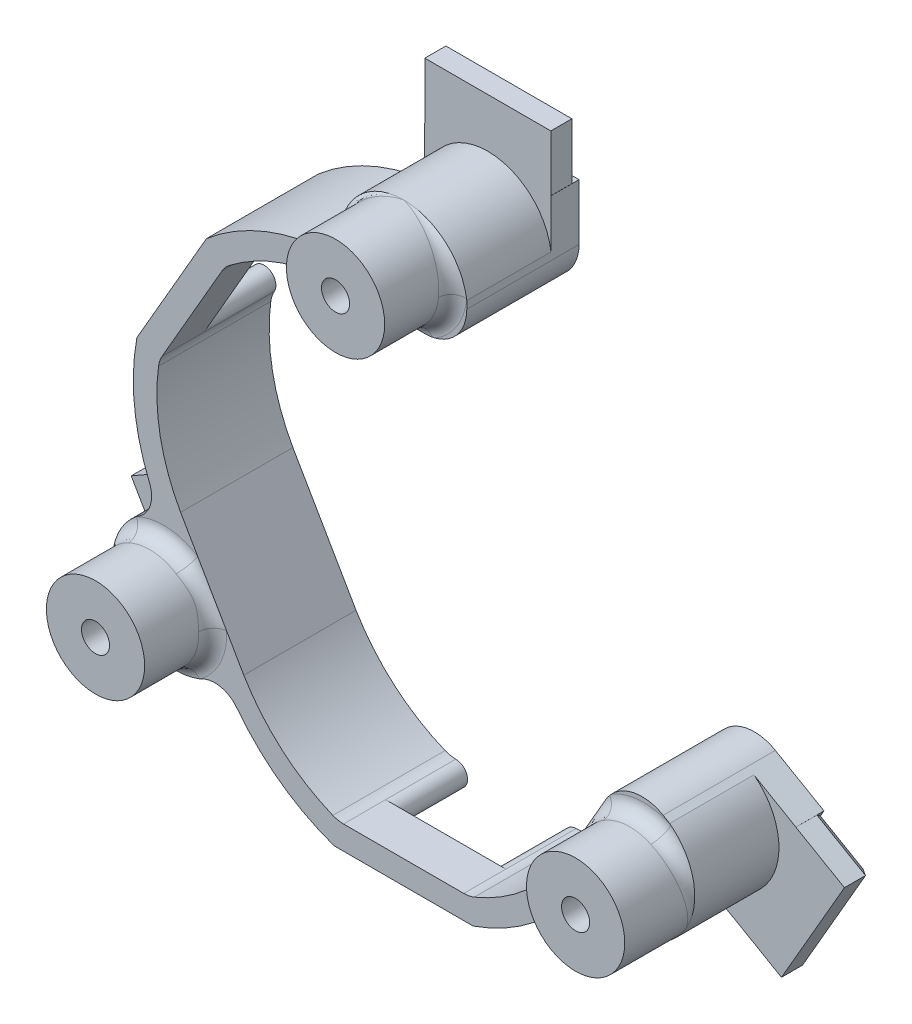
SolidWorks part; units mm, degrees
ref_plane "Front Plane" through (0, 0, 0) normal (0, 0, 1) x (1, 0, 0)
ref_plane "Top Plane" through (0, 0, 0) normal (0, 1, 0) x (1, 0, 0)
ref_plane "Right Plane" through (0, 0, 0) normal (1, 0, 0) x (0, 0, -1)
sketch "Sketch1" plane through (0, 0, 0) normal (0, 0, 1) x (1, 0, 0)
  line L0 (-4.5, 22.75) -> (4.5, 22.75) construction
  line L1 (-4.5, 22.75) -> (-4.5, 26.75)
  line L2 (-4.5, 26.75) -> (4.5, 26.75)
  line L3 (4.5, 26.75) -> (4.5, 22.75)
  line L4 (-4.5, 22.75) -> (-4.5, 15.75)
  line L5 (-4.5, 15.75) -> (4.5, 15.75)
  line L6 (4.5, 15.75) -> (4.5, 22.75)
  circle A0 centre (0, 0) radius 22.75 construction
  point P5 (0, 22.75)
  point P6 (0, 15.75)
  dimension "D1" = 45.5
  dimension "D2" = 9
  dimension "D3" = 4
  dimension "D4" = 7
extrude "Boss-Extrude1" add sketch "Sketch1" along normal blind 2
sketch "Sketch2" plane through (0, 0, 2) normal (0, 0, 1) x (1, 0, 0)
  line L0 (4.5, 15.75) -> (4.5, 26.75) construction
  line L1 (-4.5, 15.75) -> (4.5, 15.75)
  line L2 (-4.5, 15.75) -> (-4.5, 23.75)
  line L3 (-4.5, 23.75) -> (4.5, 23.75)
  line L4 (4.5, 15.75) -> (4.5, 23.75)
  line L5 (4.5, 26.75) -> (-4.5, 26.75) construction
  dimension "D1" = 3
extrude "Boss-Extrude2" add sketch "Sketch2" along normal blind 10.85
sketch "Sketch5" plane through (0, 0, 12.85) normal (0, 0, 1) x (1, 0, 0)
  line L0 (0, 15.75) -> (0, 23.75) construction
  line L1 (-4.5, 15.75) -> (4.5, 15.75) construction
  line L2 (4.5, 23.75) -> (-4.5, 23.75) construction
  circle A0 centre (0, 19.75) radius 1
  point P0 (0, 0)
  point P10 (0, 19.75)
  dimension "D2" = 2
  dimension "D1" = 19.75
extrude "Cut-Extrude1" cut sketch "Sketch5" against normal through all
sketch "Sketch17" plane through (0, 0, 0) normal (0, 0, -1) x (-1, 0, 0)
  line L0 (4.49, 26.75) -> (4.49, 22.75)
  line L1 (-4.5, 26.75) -> (4.5, 26.75) construction
  line L2 (4.49, 22.75) -> (-4.49, 22.75) construction
  line L3 (-4.49, 22.75) -> (-4.49, 26.75)
  line L4 (4.49, 22.75) -> (4.5, 22.75)
  line L5 (4.5, 26.75) -> (4.5, 15.75) construction
  line L6 (-4.5, 15.75) -> (-4.5, 26.75) construction
  line L7 (4.5, 23.75) -> (-4.5, 23.75) construction
  line L8 (4.5, 22.75) -> (4.5, 26.75)
  line L9 (4.5, 26.75) -> (4.49, 26.75)
  line L10 (-4.49, 22.75) -> (-4.5, 22.75)
  line L11 (-4.5, 22.75) -> (-4.5, 26.75)
  line L12 (-4.5, 26.75) -> (-4.49, 26.75)
  point P4 (4.5, 23.75)
  point P7 (-4.5, 23.75)
  dimension "D1" = 1
  dimension "D2" = 0.01
  dimension "D3" = 0.01
extrude "Cut-Extrude7" cut sketch "Sketch17" against normal up to surface (2 mm away) up to face at (1.125, 25.25, 2)
ref_axis "Axis1" through (0, 0, -0.6425) along (0, 0, 1)
pattern_circular "CirPattern1" count 3 over 360 about axis through (0, 0, -0.6425) along (0, 0, 1) of bodies 124 104
sketch "Sketch3" plane through (0, 0, 0) normal (0, 0, -1) x (-1, 0, 0)
  line L0 (-11.3899, -11.7721) -> (11.3899, -11.7721) construction
  line L2 (0, 0) -> (-13.6399, -7.875) construction
  line L3 (-15.8899, -3.9779) -> (-11.3899, -11.7721) construction
  line L4 (0, 0) -> (-4.0622, -15.1603) construction
  line L5 (-11.3899, -11.7721) -> (-17.4521, -15.2721) construction
  line L6 (-12.8449, -12.6122) -> (-11.3899, -11.7721)
  line L7 (12.8449, -12.6122) -> (11.3899, -11.7721)
  line L8 (0, 0) -> (13.6399, -7.875) construction
  line L9 (11.3899, -11.7721) -> (15.8899, -3.9779) construction
  line L10 (17.3449, -4.8179) -> (15.8899, -3.9779)
  line L11 (4.5, 17.4301) -> (4.5, 15.75)
  line L14 (4.9592, -19.0834) -> (-4.9592, -19.0834)
  line L15 (-4.6632, -17.4034) -> (4.6632, -17.4034)
  line L18 (17.4034, 4.6632) -> (12.7402, 12.7402)
  line L19 (14.0471, 13.8365) -> (19.0064, 5.2469)
  arc A0 (-11.3899, -11.7721) -> (-4.6632, -17.4034) centre (0, -5) ccw
  arc A1 (-12.8449, -12.6122) -> (-4.9592, -19.0834) centre (0, -5) ccw
  arc A4 (11.3899, -11.7721) -> (4.6632, -17.4034) centre (0, -5) cw
  arc A5 (12.8449, -12.6122) -> (4.9592, -19.0834) centre (0, -5) cw
  arc A6 (17.3449, -4.8179) -> (19.0064, 5.2469) centre (4.3301, 2.5) ccw
  arc A7 (15.8899, -3.9779) -> (17.4034, 4.6632) centre (4.3301, 2.5) ccw
  arc A10 (4.5, 17.4301) -> (14.0471, 13.8365) centre (4.3301, 2.5) cw
  arc A11 (4.5, 15.75) -> (12.7402, 12.7402) centre (4.3301, 2.5) cw
  point P7 (0, -5)
  point P11 (0, -19.5)
  point P22 (0, -11.7721)
  dimension "D4" = 1.68
  dimension "D5" = 1.68
  dimension "D1" = 5
  dimension "D2" = 19.5
  dimension "D3" = 45
extrude "Boss-Extrude3" add sketch "Sketch3" against normal blind 8
sketch "Sketch13" plane through (0, 0, 12.85) normal (0, 0, 1) x (1, 0, 0)
  circle A0 centre (-17.104, -9.875) radius 3.5
  circle A1 centre (-17.104, -9.875) radius 6.0208
  circle A2 centre (0, 19.75) radius 3.5
  circle A3 centre (0, 19.75) radius 6.0208
  circle A4 centre (17.104, -9.875) radius 3.5
  circle A5 centre (17.104, -9.875) radius 6.0208
extrude "Cut-Extrude4" cut sketch "Sketch13" against normal up to surface (4.85 mm away) up to face at (0, -15.5346, 8)
fillet "Fillet1" radius 2 4 edges at (12.8449, -12.6122, 4) (-12.8449, -12.6122, 4) (-17.3449, -4.8179, 4) (-4.5, 17.4301, 4)
sketch "Sketch16" plane through (0, 0, 8) normal (0, 0, 1) x (1, 0, 0)
  line L0 (4.5, 19.2915) -> (4.5, 24.6619)
  line L1 (-4.5, 19.2915) -> (-4.5, 24.6619)
  line L2 (-4.5, 24.6619) -> (4.5, 24.6619)
  line L3 (15.8899, -3.9779) -> (22.8181, -7.9779) construction
  line L4 (-17.104, -9.875) -> (-20.5681, -11.875) construction
  line L5 (-18.3181, -15.7721) -> (-22.8181, -7.9779) construction
  line L6 (17.104, -9.875) -> (20.5681, -11.875) construction
  line L7 (22.8181, -7.9779) -> (18.3181, -15.7721) construction
  line L8 (0, 19.75) -> (0, 23.75) construction
  line L9 (-4.5, 23.75) -> (4.5, 23.75) construction
  arc A0 (4.5, 19.2915) -> (-4.5, 19.2915) centre (0, 18.713) ccw
  arc A1 (-18.9569, -5.7486) -> (-14.4569, -13.5428) centre (-16.2059, -9.3565) ccw
  arc A2 (-14.4569, -13.5428) -> (-18.9569, -5.7486) centre (-19.7218, -11.3864) cw
  arc A3 (14.4569, -13.5428) -> (18.9569, -5.7486) centre (16.2059, -9.3565) ccw
  arc A4 (18.9569, -5.7486) -> (14.4569, -13.5428) centre (19.3047, -11.1456) cw
  circle A5 centre (-17.104, -9.875) radius 3.5 construction
  circle A6 centre (17.104, -9.875) radius 3.5 construction
  circle A7 centre (0, 19.75) radius 3.5 construction
  point P26 (-20.1351, -11.625)
  point P34 (20.1351, -11.625)
  point P42 (0, 23.25)
  line M31 (-4.5, 23.75) -> (-4.5, 19.2915)
  line M37 (-18.9569, -5.7486) -> (-22.8181, -7.9779)
  line M38 (-22.8181, -7.9779) -> (-18.3181, -15.7721)
  line M39 (-18.3181, -15.7721) -> (-14.4569, -13.5428)
  line M45 (14.4569, -13.5428) -> (18.3181, -15.7721)
extrude "Cut-Extrude5" cut sketch "Sketch16" against normal up to surface (6 mm away) contours A3 M45 | A0 L0 M31 | A1 M37 M38 M39 region at (0, 23.2809, 8) region at (-20.2481, -11.6903, 8) region at (20.9999, -12.1243, 8) up to face at (21.3059, -13.5971, 2)
fillet "Fillet3" radius 2 4 edges at (4.6632, -17.4034, 4) (-4.6632, -17.4034, 4) (-17.4034, 4.6632, 4) (-12.7402, 12.7402, 4)
fillet "Fillet8" radius 1 3 edges at (13.604, -9.875, 8) (-20.604, -9.875, 8) (-3.5, 19.75, 8)
chamfer "Chamfer1" distance 0.5 angle 45 9 edges at (23.1662, -13.375, 0) (0, 26.75, 0) (-23.1662, -13.375, 0) (-4.49, 24.75, 0) (4.49, 24.75, 0) (23.6791, -8.4865, 0) (19.1891, -16.2635, 0) (-19.1891, -16.2635, 0) (-23.6791, -8.4865, 0) tangent propagation no
chamfer "Chamfer2" [suppressed] distance 0.2 angle 45
sketch "Sketch19" plane through (0, 0, 0) normal (0, 0, -1) x (-1, 0, 0)
  line L0 (12.9297, 12.412) -> (14.3846, 13.252)
  line L1 (19.0064, 5.2469) -> (14.0471, 13.8365) construction
  line L2 (17.214, 4.9914) -> (18.6689, 5.8314)
  line L3 (18.6689, 5.8314) -> (14.3846, 13.252)
  line L4 (12.9297, 12.412) -> (17.214, 4.9914)
  line L10 (4.2843, -17.4034) -> (4.2843, -19.0834)
  line L11 (-4.9592, -19.0834) -> (4.9592, -19.0834) construction
  line L12 (-4.2843, -17.4034) -> (-4.2843, -19.0834)
  line L13 (-4.2843, -19.0834) -> (4.2843, -19.0834)
  line L14 (4.2843, -17.4034) -> (-4.2843, -17.4034)
extrude "Cut-Extrude8" cut sketch "Sketch19" against normal blind 5
sketch "Sketch20" plane through (0, 0, 0) normal (0, 0, -1) x (-1, 0, 0)
  line L0 (14.3846, 13.252) -> (12.9297, 12.412) construction
  line L1 (17.214, 4.9914) -> (18.6689, 5.8314) construction
  line L2 (4.2843, -19.0834) -> (4.2843, -17.4034) construction
  line L3 (-4.2843, -17.4034) -> (-4.2843, -19.0834) construction
  circle A0 centre (13.6571, 12.832) radius 0.84
  circle A1 centre (17.9414, 5.4114) radius 0.84
  circle A2 centre (4.2843, -18.2434) radius 0.84
  circle A3 centre (-4.2843, -18.2434) radius 0.84
extrude "Boss-Extrude8" add sketch "Sketch20" against normal up to surface (5 mm away) up to face at (0, -18.2434, 5)
fillet "Fillet12" radius 3 2 edges at (15.8899, -3.9779, 4) (4.5, 15.75, 4)
sketch "Sketch6" plane through (0, 0, 0) normal (0, 0, -1) x (-1, 0, 0)
  line L0 (7.1492, -21.7889) -> (2.9426, -12.7167)
  line L1 (2.9426, -12.7167) -> (-2.9668, -12.7167)
  line L2 (-2.9668, -12.7167) -> (-7.125, -21.7889)
  line L3 (-7.125, -21.7889) -> (7.1492, -21.7889)
  line L4 (-15.3072, 17.0648) -> (-22.4443, 4.703)
  line L5 (-9.5296, 8.9277) -> (-15.3072, 17.0648)
  line L6 (-22.4443, 4.703) -> (-12.4843, 3.81)
  line L7 (-12.4843, 3.81) -> (-9.5296, 8.9277)
  line L8 (22.4322, 4.724) -> (15.2951, 17.0858)
  line L9 (12.4964, 3.789) -> (22.4322, 4.724)
  line L10 (15.2951, 17.0858) -> (9.5417, 8.9067)
  line L11 (9.5417, 8.9067) -> (12.4964, 3.789)
  line L12 (0, 0) -> (2.9426, -12.7167) construction
  line L13 (4.2843, -17.4034) -> (-4.2843, -17.4034) construction
  dimension "D1" = 10
  dimension "D2" = 13.0527
extrude "Cut-Extrude2" [suppressed] cut sketch "Sketch6" against normal blind 5
sketch "Sketch9" [suppressed] plane through (0, 0, 0) normal (0, 0, -1) x (-1, 0, 0)
  line L0 (-5.0459, -17.2528) -> (-7.7731, -16.0028)
  line L1 (-5.0459, -17.2528) -> (-5.8792, -19.0709)
  line L2 (-7.7731, -16.0028) -> (-8.6064, -17.8209)
  line L3 (-5.8792, -19.0709) -> (-8.6064, -17.8209)
  line L4 (5.0459, -17.2528) -> (7.7675, -15.9908)
  line L5 (5.0459, -17.2528) -> (5.8872, -19.0672)
  line L6 (7.7675, -15.9908) -> (8.6089, -17.8052)
  line L7 (5.8872, -19.0672) -> (8.6089, -17.8052)
  line L8 (17.4643, 4.2565) -> (17.7453, 1.2697)
  line L9 (17.4643, 4.2565) -> (19.4555, 4.4439)
  line L10 (17.7453, 1.2697) -> (19.7365, 1.4571)
  line L11 (19.4555, 4.4439) -> (19.7365, 1.4571)
  line L12 (12.4184, 12.9962) -> (9.9647, 14.7223)
  line L13 (12.4184, 12.9962) -> (13.5691, 14.6321)
  line L14 (9.9647, 14.7223) -> (11.1153, 16.3581)
  line L15 (13.5691, 14.6321) -> (11.1153, 16.3581)
  line L16 (-12.4184, 12.9962) -> (-9.9723, 14.7331)
  line L17 (-12.4184, 12.9962) -> (-13.5763, 14.627)
  line L18 (-9.9723, 14.7331) -> (-11.1301, 16.3638)
  line L19 (-13.5763, 14.627) -> (-11.1301, 16.3638)
  line L20 (-17.4643, 4.2565) -> (-17.7322, 1.2685)
  line L21 (-17.4643, 4.2565) -> (-19.4563, 4.4351)
  line L22 (-17.7322, 1.2685) -> (-19.7242, 1.4471)
  line L23 (-19.4563, 4.4351) -> (-19.7242, 1.4471)
  line L24 (5.7532, -18.7782) -> (5.0459, -17.2528) construction
  line L27 (-5.0459, -17.2528) -> (-5.7464, -18.781) construction
  line L28 (-19.139, 4.4067) -> (-17.4643, 4.2565) construction
  line L29 (-12.4184, 12.9962) -> (-13.3917, 14.367) construction
  line L30 (17.4643, 4.2565) -> (19.138, 4.414) construction
  line L31 (13.3858, 14.3715) -> (12.4184, 12.9962) construction
  dimension "D1" = 2
  dimension "D2" = 2
  dimension "D3" = 2
  dimension "D4" = 2
  dimension "D5" = 2
  dimension "D6" = 2
  dimension "D7" = 3
  dimension "D8" = 3
  dimension "D9" = 3
  dimension "D10" = 3
  dimension "D11" = 3
  dimension "D12" = 3
extrude "Boss-Extrude6" [suppressed] add sketch "Sketch9" against normal up to surface (8 mm away) up to face at (0, -14.6473, 8)
chamfer "Chamfer3" [suppressed] distance 1.38 angle 45
sketch "Sketch11" [suppressed] plane through (0, 0, 8) normal (0, 0, 1) x (1, 0, 0)
  line L0 (19.4741, 4.4367) -> (13.5843, 14.6383)
  line L1 (13.5843, 14.6383) -> (13.3917, 14.367)
  line L2 (13.3917, 14.367) -> (19.139, 4.4067)
  line L3 (19.139, 4.4067) -> (19.4741, 4.4367)
  line L4 (5.6034, -18.2634) -> (-5.6034, -18.2634)
  line L5 (-5.6034, -18.2634) -> (-5.4638, -18.0104)
  line L6 (-5.4638, -18.0104) -> (5.4638, -18.0104)
  line L7 (5.4638, -18.0104) -> (5.6034, -18.2634)
  line L8 (-13.5794, 14.6467) -> (-19.4692, 4.4452)
  line L9 (-19.4692, 4.4452) -> (-19.138, 4.414)
  line L10 (-19.138, 4.414) -> (-13.3858, 14.3715)
  line L11 (-13.3858, 14.3715) -> (-13.5794, 14.6467)
  line L12 (-19.0064, 5.2469) -> (-14.0471, 13.8365) construction
  line L13 (-13.5691, 14.6321) -> (-13.3858, 14.3715) construction
  line L14 (-19.138, 4.414) -> (-19.4555, 4.4439) construction
  line L15 (4.9592, -19.0834) -> (-4.9592, -19.0834) construction
  line L16 (-5.8872, -19.0672) -> (-5.7532, -18.7782) construction
  line L17 (5.7464, -18.781) -> (5.8792, -19.0709) construction
  line L18 (14.0471, 13.8365) -> (19.0064, 5.2469) construction
  line L19 (13.3917, 14.367) -> (13.5763, 14.627) construction
  line L20 (19.4563, 4.4351) -> (19.139, 4.4067) construction
extrude "Boss-Extrude7" [suppressed] add sketch "Sketch11" against normal up to surface (3 mm away) up to face at (-15.7993, 9.1217, 5)
sketch "Sketch7" [suppressed] plane through (0, 0, 0) normal (0, 0, -1) x (-1, 0, 0)
  line L0 (18.0621, 4.3128) -> (12.7639, 13.4874)
  line L1 (18.0621, 4.3128) -> (17.4653, 4.2566)
  line L2 (12.7639, 13.4874) -> (12.4184, 12.9962)
  line L3 (17.4653, 4.2566) -> (12.4184, 12.9962)
  line L4 (-18.0624, 4.3102) -> (-12.766, 13.4858)
  line L5 (-18.0624, 4.3102) -> (-17.4643, 4.2565)
  line L6 (-12.766, 13.4858) -> (-12.419, 12.9971)
  line L7 (-17.4643, 4.2565) -> (-12.419, 12.9971)
  line L8 (5.2985, -17.7976) -> (-5.2961, -17.7986)
  line L9 (5.2985, -17.7976) -> (5.0459, -17.2528)
  line L10 (-5.2961, -17.7986) -> (-5.0463, -17.2537)
  line L11 (5.0459, -17.2528) -> (-5.0463, -17.2537)
  line L12 (-12.4184, 12.9962) -> (-13.5763, 14.627) construction
  line L13 (-5.0459, -17.2528) -> (-5.8792, -19.0709) construction
  line L14 (17.4643, 4.2565) -> (19.4555, 4.4439) construction
extrude "Boss-Extrude4" [suppressed] add sketch "Sketch7" against normal blind 0.2
sketch "Sketch8" [suppressed] plane through (0, 0, 0) normal (0, 0, -1) x (-1, 0, 0)
  line L3 (-5.2961, -17.7986) -> (5.2985, -17.7976) construction
  line L4 (-12.766, 13.4858) -> (-18.0624, 4.3102) construction
  line L5 (18.0621, 4.3128) -> (12.7639, 13.4874) construction
  circle A0 centre (0.0012, -17.7981) radius 5
  circle A1 centre (-15.4142, 8.898) radius 5
  circle A2 centre (15.413, 8.9001) radius 5
  dimension "D1" = 10
  dimension "D2" = 10
  dimension "D3" = 10
extrude "Boss-Extrude5" [suppressed] add sketch "Sketch8" against normal up to surface (0.2 mm away) up to face at (0, -14.6473, 8)
sketch "Sketch12" plane through (0, 0, 8) normal (0, 0, 1) x (1, 0, 0)
  line L0 (-21.5268, 0.8815) -> (-11.5268, 18.202)
  line L1 (-11.5268, 18.202) -> (-16.7229, 21.202)
  line L2 (-16.7229, 21.202) -> (-26.7229, 3.8815)
  line L3 (-26.7229, 3.8815) -> (-21.5268, 0.8815)
  line L4 (-19.0064, 5.2469) -> (-14.0471, 13.8365) construction
  line L5 (11.5268, 18.202) -> (21.5268, 0.8815)
  line L6 (11.5268, 18.202) -> (16.7229, 21.202)
  line L7 (21.5268, 0.8815) -> (26.7229, 3.8815)
  line L8 (16.7229, 21.202) -> (26.7229, 3.8815)
  line L9 (14.0471, 13.8365) -> (19.0064, 5.2469) construction
  line L10 (10, -19.0834) -> (-10, -19.0834)
  line L11 (10, -19.0834) -> (10, -25.0834)
  line L12 (-10, -19.0834) -> (-10, -25.0834)
  line L13 (10, -25.0834) -> (-10, -25.0834)
  line L14 (4.9592, -19.0834) -> (-4.9592, -19.0834) construction
  point P2 (-16.5268, 9.5417)
  point P7 (16.5268, 9.5417)
  point P14 (0, -19.0834)
  dimension "D1" = 20
  dimension "D2" = 20
  dimension "D3" = 20
  dimension "D4" = 6
  dimension "D5" = 6
  dimension "D6" = 6
extrude "Cut-Extrude3" [suppressed] cut sketch "Sketch12" against normal up to surface (8 mm away) up to face at (1, 19.75, 0)
fillet "Fillet6" [suppressed] radius 2
fillet "Fillet10" [suppressed] radius 2
fillet "Fillet11" [suppressed] radius 0.6
